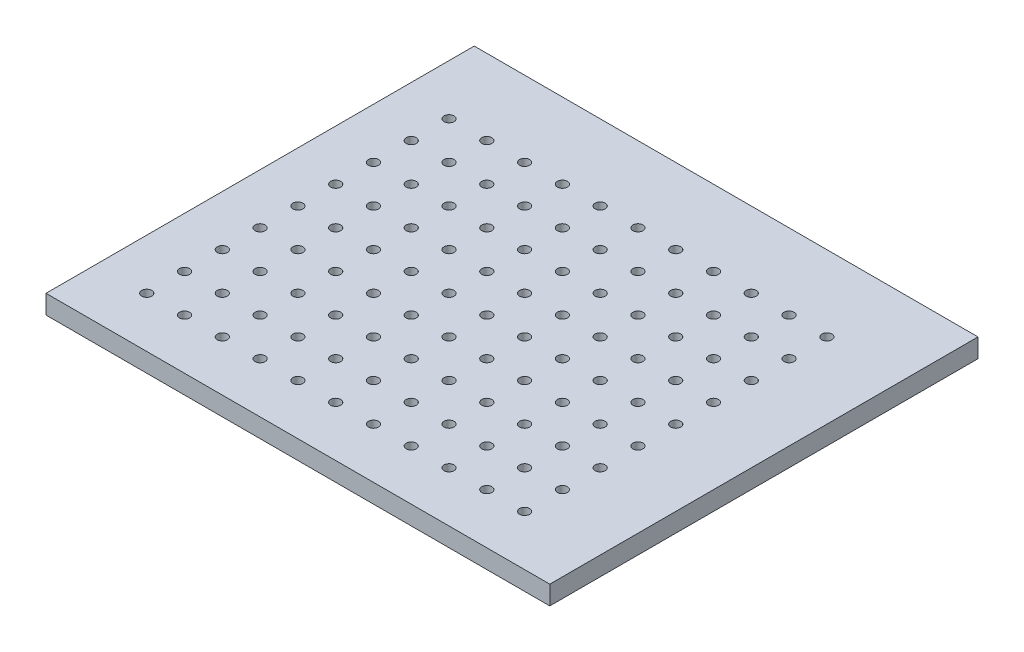
SolidWorks part; units mm, degrees
material "Balsa"
ref_plane "Plano frontal" through (0, 0, 0) normal (0, 0, 1) x (1, 0, 0)
ref_plane "Plano superior" through (0, 0, 0) normal (0, 1, 0) x (1, 0, 0)
ref_plane "Plano direito" through (0, 0, 0) normal (1, 0, 0) x (0, 0, -1)
sketch "Esboço1" plane through (0, 0, 0) normal (0, 1, 0) x (1, 0, 0)
  line L1 (-200, -170) -> (200, -170)
  line L2 (-200, -170) -> (-200, 170)
  line L3 (-200, 170) -> (200, 170)
  line L4 (200, -170) -> (200, 170)
  line L5 (-200, -170) -> (200, 170) construction
  line L6 (-200, 170) -> (200, -170) construction
  point P0 (0, 0)
  dimension "D1" = 340
  dimension "D2" = 400
extrude "Ressalto-extrusão1" add sketch "Esboço1" along normal blind 15
sketch "Esboço2" plane through (0, 15, 0) normal (0, 1, 0) x (1, 0, 0)
  line L0 (-200, -170) -> (200, -170) construction
  line L1 (-200, 170) -> (-200, -170) construction
  circle A0 centre (-160, -130) radius 4
  dimension "D1" = 8
  dimension "D2" = 40
  dimension "D3" = 40
extrude "Corte-extrusão1" cut sketch "Esboço2" against normal through all
pattern_linear "Padrão linear1" count 11 spacing 30 along (1, 0, 0) count 9 spacing 30 along (0, 0, -1) of "Corte-extrusão1"
ref_plane "Plane1" through (0, 0, 0) normal (0, 0, 1) x (1, 0, 0)
